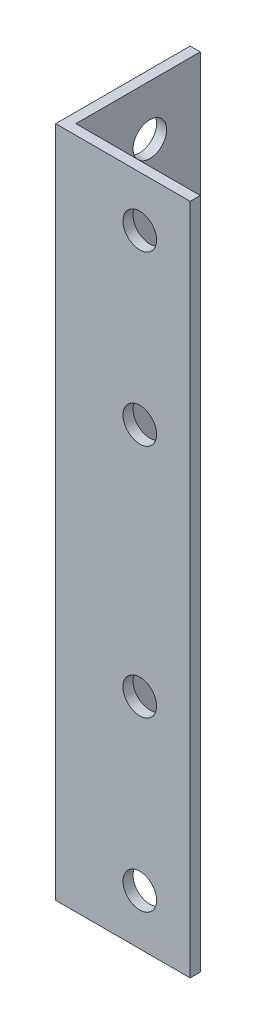
SolidWorks part; units mm, degrees
ref_plane "Спереди" through (0, 0, 0) normal (0, 0, 1) x (1, 0, 0)
ref_plane "Сверху" through (0, 0, 0) normal (0, 1, 0) x (1, 0, 0)
ref_plane "Справа" through (0, 0, 0) normal (1, 0, 0) x (0, 0, -1)
sketch "Эскиз1" plane through (0, 0, 0) normal (0, 1, 0) x (1, 0, 0)
  line L0 (0, 40) -> (0, 0)
  line L1 (0, 0) -> (40, 0)
  dimension "D1" = 40
extrude "Вытянуть-Тонкостенный1" add sketch "Эскиз1" along normal blind 200 thin thin type one direction reverse wall 3
sketch "Эскиз2" plane through (0, 0, 0) normal (-1, 0, 0) x (0, 0, 1)
  line L0 (-40, 100) -> (5.7928, 100) construction
  line L1 (-40, 200) -> (-40, 0) construction
  circle A0 centre (-25, 15) radius 5
  circle A1 centre (-25, 65) radius 5
  circle A4 centre (-25, 135) radius 5
  circle A5 centre (-25, 185) radius 5
  point P6 (-40, 100)
  dimension "D1" = 2
extrude "Вырез-Вытянуть1" cut sketch "Эскиз2" against normal through all
sketch "Эскиз3" plane through (0, 0, 0) normal (0, 0, 1) x (1, 0, 0)
  line L0 (0, 100) -> (59.4602, 100) construction
  line L1 (0, 200) -> (0, 0) construction
  circle A0 centre (25, 15) radius 5
  circle A1 centre (25, 65) radius 5
  circle A2 centre (25, 135) radius 5
  circle A3 centre (25, 185) radius 5
  dimension "D1" = 2
extrude "Вырез-Вытянуть2" cut sketch "Эскиз3" against normal through all
